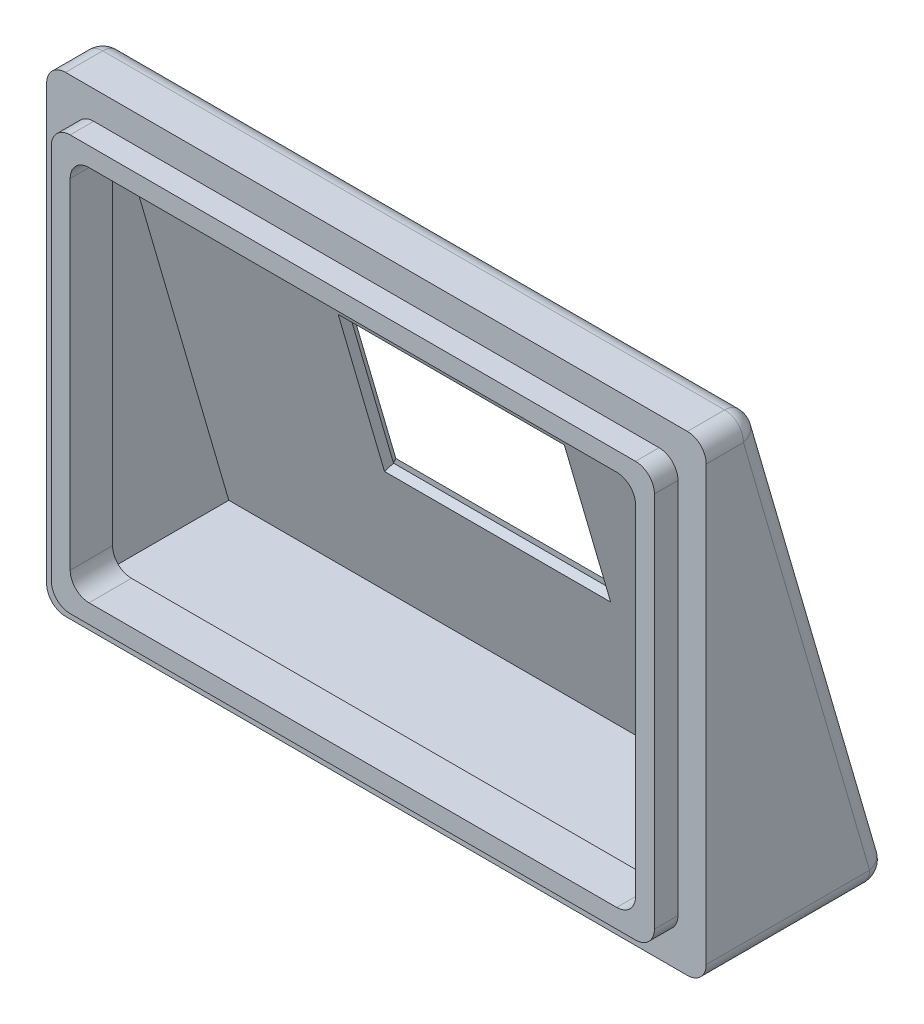
SolidWorks part; units mm, degrees
ref_plane "Front Plane" through (0, 0, 0) normal (0, 0, 1) x (1, 0, 0)
ref_plane "Top Plane" through (0, 0, 0) normal (0, 1, 0) x (1, 0, 0)
ref_plane "Right Plane" through (0, 0, 0) normal (1, 0, 0) x (0, 0, -1)
sketch "Sketch1" plane through (0, 0, 0) normal (1, 0, 0) x (0, 0, -1)
  line L0 (0, 0) -> (0, 50)
  line L1 (0, 50) -> (5.4517, 50)
  line L2 (0, 0) -> (20, 0)
  line L3 (5.4517, 50) -> (20, 0)
  dimension "D1" = 50
  dimension "D2" = 20
extrude "Boss-Extrude1" add sketch "Sketch1" along normal blind 70
sketch "Sketch2" plane through (0, 0, 0) normal (0, 0, 1) x (1, 0, 0)
  line L0 (67, 47) -> (3, 47)
  line L1 (3, 47) -> (3, 3)
  line L2 (3, 3) -> (67, 3)
  line L3 (67, 3) -> (67, 47)
extrude "Boss-Extrude2" add sketch "Sketch2" along normal blind 2.5
shell "Shell1" thickness 2 removed face at (35, 25, 2.5)
fillet "Fillet1" radius 2 12 edges at (65, 45, 0.25) (65, 5, 0.25) (5, 45, 0.25) (5, 5, 0.25) (70, 0, -10) (67, 3, 1.25) (70, 50, -2.7259) (67, 47, 1.25) (0, 0, -10) (0, 50, -2.7259) (3, 3, 1.25) (3, 47, 1.25)
fillet "Fillet2" radius 2 8 edges at (69.4142, 49.4142, -5.6222) (35, 50, -5.4517) (0.5858, 49.4142, -5.6222) (0, 25, -12.7259) (0.5858, 0.5858, -19.8296) (35, 0, -20) (69.4142, 0.5858, -19.8296) (70, 25, -12.7259)
sketch "Sketch3" plane through (0, 5.3651, -18.4389) normal (0, 0.2794, -0.9602) x (-1, 0, 0)
  line L0 (-68, 46.9053) -> (-2, 46.9053) construction
  line L1 (-47, 30.7029) -> (-23, 30.7029)
  line L2 (-47, 30.7029) -> (-47, 13.1076)
  line L3 (-47, 13.1076) -> (-23, 13.1076)
  line L4 (-23, 30.7029) -> (-23, 13.1076)
  line L5 (-70, -2.9227) -> (-70, 44.9849) construction
  point P4 (-23, 21.9053)
  point P7 (-35, 30.7029)
  dimension "D1" = 24
  dimension "D2" = 17.5953
  dimension "D3" = 25
  dimension "D4" = 35
extrude "Cut-Extrude1" cut sketch "Sketch3" against normal blind 2.5
chamfer "Chamfer3" distance 1 angle 45 4 edges at (35, 17.9508, -14.7769) (23, 26.3981, -12.3191) (35, 34.8455, -9.8612) (47, 26.3981, -12.3191)
sketch "Sketch4" plane through (0, 0, 0) normal (0, -1, 0) x (1, 0, 0)
  line L0 (0, -17.3351) -> (0, 0) construction
  line L1 (70, 0) -> (70, -17.3351) construction
  circle A0 centre (6.5, -11.1207) radius 2.5
  circle A1 centre (63.5, -11.1207) radius 2.5
  dimension "D1" = 5
  dimension "D2" = 5
  dimension "D3" = 6.5
  dimension "D4" = 6.5
extrude "Boss-Extrude3" add sketch "Sketch4" along normal blind 2
